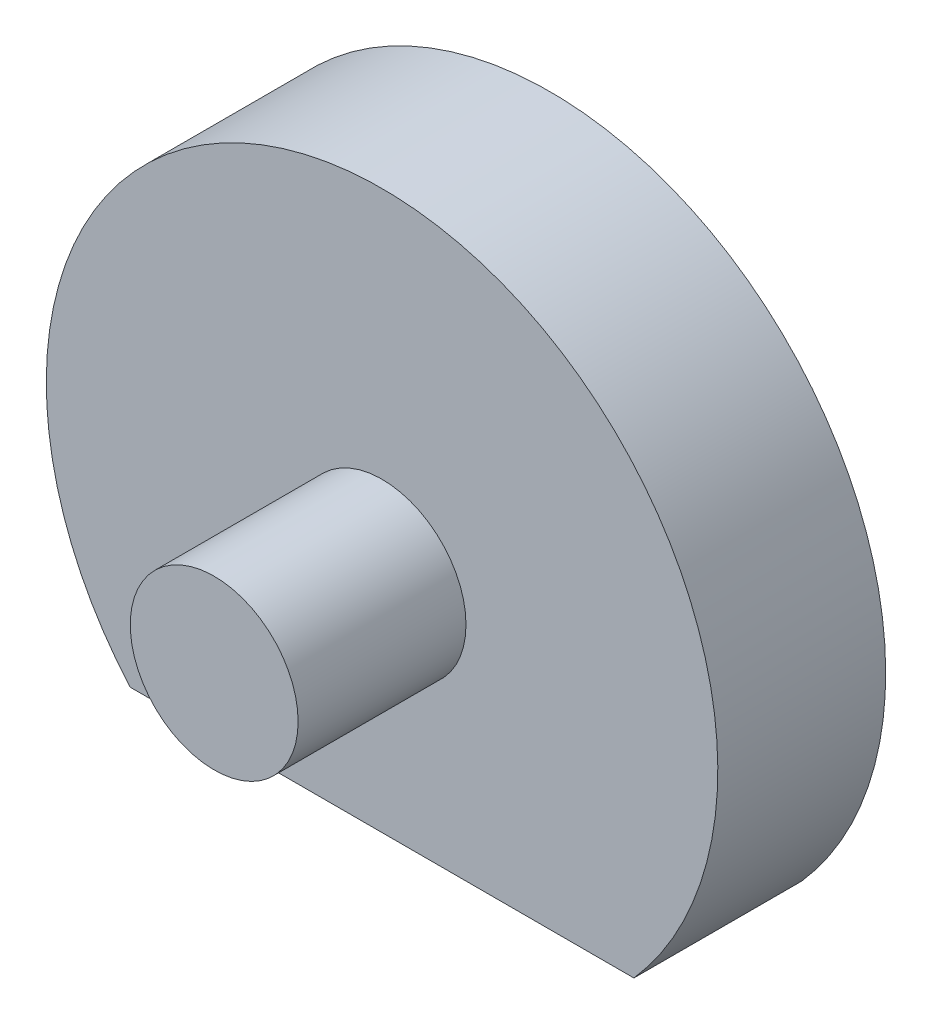
SolidWorks part; units mm, degrees
ref_plane "Front Plane" through (0, 0, 0) normal (0, 0, 1) x (1, 0, 0)
ref_plane "Top Plane" through (0, 0, 0) normal (0, 1, 0) x (1, 0, 0)
ref_plane "Right Plane" through (0, 0, 0) normal (1, 0, 0) x (0, 0, -1)
sketch "Sketch1" plane through (0, 0, 0) normal (0, 0, 1) x (1, 0, 0)
  line L0 (-87.0647, 20.7435) -> (-72.0647, 20.7435)
  circle A0 centre (-79.5647, 27.3579) radius 2.5
  arc A1 (-72.0647, 20.7435) -> (-87.0647, 20.7435) centre (-79.5647, 27.3579) ccw
  dimension "D1" = 20
  dimension "D2" = 5
  dimension "D3" = 15
extrude "Boss-Extrude1" add sketch "Sketch1" against normal blind 10 contours A0 region at (-79.5647, 27.3579, 0)
extrude "Boss-Extrude2" add sketch "Sketch1<3>" against normal blind 5 from offset 5 contours L0 A1 A0 region at (-79.5647, 37.0979, 0) offset against normal yes
sketch "Sketch1<3>" plane through (0, 0, 0) normal (0, 0, 1) x (1, 0, 0) same geometry as "Sketch1"
